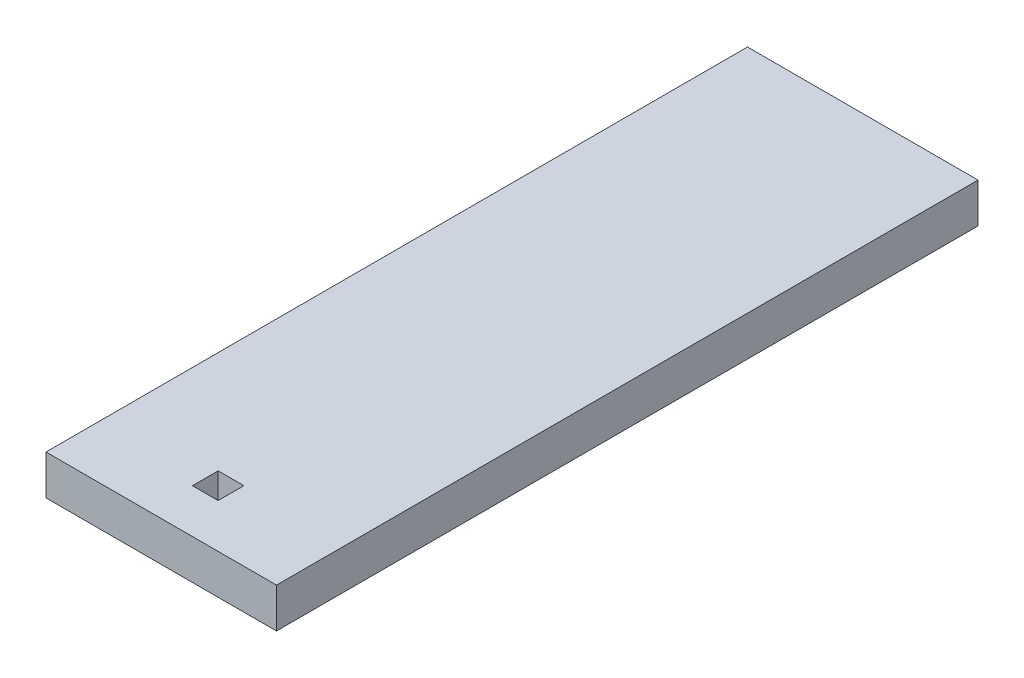
SolidWorks part; units mm, degrees
material "Acrylic (Medium-high impact)"
ref_plane "Front Plane" through (0, 0, 0) normal (0, 0, 1) x (1, 0, 0)
ref_plane "Top Plane" through (0, 0, 0) normal (0, 1, 0) x (1, 0, 0)
ref_plane "Right Plane" through (0, 0, 0) normal (1, 0, 0) x (0, 0, -1)
sketch "Sketch1" plane through (0, 0, 0) normal (0, 1, 0) x (1, 0, 0)
  line L0 (0, 28) -> (0, 0) construction
  line L1 (-9.2, 28) -> (9.2, 28)
  line L2 (-9.2, 28) -> (-9.2, -28)
  line L3 (-9.2, -28) -> (9.2, -28)
  line L4 (9.2, 28) -> (9.2, -28)
  line L5 (0, -22.433) -> (0, 0) construction
  line L6 (-1.025, -22.433) -> (1.025, -22.433)
  line L7 (-1.025, -22.433) -> (-1.025, -24.483)
  line L8 (-1.025, -24.483) -> (1.025, -24.483)
  line L9 (1.025, -22.433) -> (1.025, -24.483)
  line L11 (-9.2, 28) -> (-12.375, 28)
  line L12 (-9.2, 28) -> (-9.2, -28)
  line L13 (-9.2, -28) -> (-12.375, -28)
  line L14 (-12.375, 28) -> (-12.375, -28)
  point P11 (1.025, -23.458)
  point P14 (9.2, 0)
  dimension "D1" = 18.4
  dimension "D2" = 56
  dimension "D3" = 51.458
  dimension "D4" = 2.05
  dimension "D5" = 3.175
extrude "Boss-Extrude1" add sketch "Sketch1" along normal blind 3.175 contours L4 L1 L2 L3 L6 L9 L8 L7 | L11 L14 L13 L2 region at (0, 0, -0.0961) region at (-10.7875, 0, 0)
sketch "Sketch2" plane through (0, 3.175, 0) normal (0, 1, 0) x (1, 0, 0)
  line L0 (-12.375, -28) -> (9.2, -28) construction
  line L1 (-12.375, 28) -> (-9.2, 28)
  line L2 (-12.375, 28) -> (-12.375, -28)
  line L3 (-12.375, -28) -> (-9.2, -28)
  line L4 (-9.2, 28) -> (-9.2, -28)
  dimension "D1" = 3.175
extrude "Cut-Extrude1" cut sketch "Sketch2" against normal through all
equation "\"bottomThickness\"= .220in"
equation "\"wallThickness\"= .125in"
equation "\"D1@Sketch2\"=\"wallThickness\""
equation "\"D1@Boss-Extrude1\"=\"wallThickness\""
